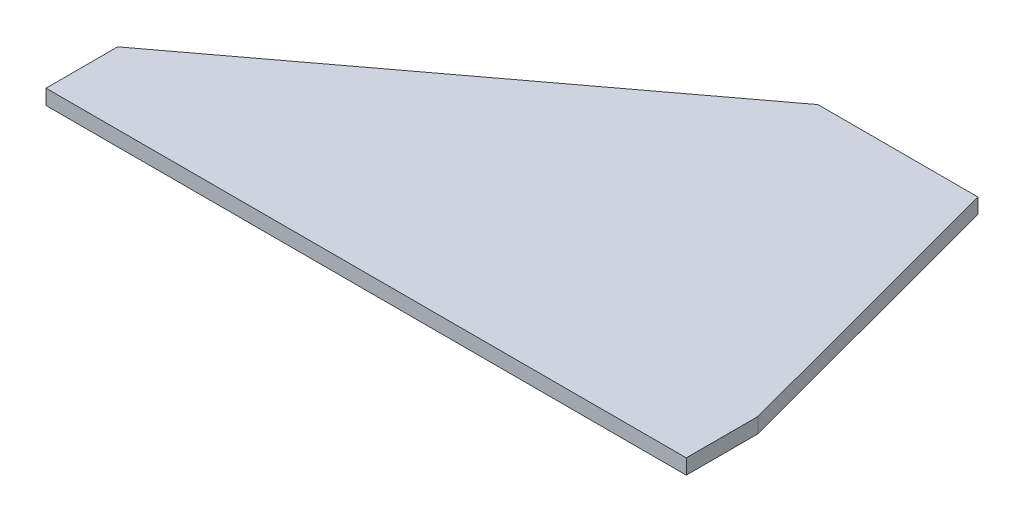
SolidWorks part; units mm, degrees
ref_plane "Front Plane" through (0, 0, 0) normal (0, 0, 1) x (1, 0, 0)
ref_plane "Top Plane" through (0, 0, 0) normal (0, 1, 0) x (1, 0, 0)
ref_plane "Right Plane" through (0, 0, 0) normal (1, 0, 0) x (0, 0, -1)
sketch "Sketch1" plane through (0, 0, 0) normal (0, 1, 0) x (1, 0, 0)
  line L0 (0, 0) -> (0, 22.733)
  line L1 (0, 22.733) -> (127, 117.983)
  line L2 (127, 117.983) -> (177.8, 117.983)
  line L3 (177.8, 117.983) -> (203.2, 22.733)
  line L4 (203.2, 22.733) -> (203.2, 0)
  line L5 (203.2, 0) -> (0, 0)
  line L6 (0, 22.733) -> (0, 117.983) construction
  line L7 (0, 117.983) -> (127, 117.983) construction
  dimension "D1" = 203.2
  dimension "D2" = 22.733
  dimension "D3" = 50.8
  dimension "D4" = 95.25
  dimension "D5" = 127
extrude "Boss-Extrude1" add sketch "Sketch1" along normal blind 2.3813 and the other way blind 2.3813 contours L3 L4 L5 L0 L1 L2
equation "\"Root Chord\"= 8"
equation "\"Tip Chord\"=2"
equation "\"Height\"=3.75"
equation "\"Sweep Length\"=5"
equation "\"Fin Thickness\"= 3 / 16"
equation "\"Bevel Depth\"= 1 / 16"
equation "\"Bevel Width\"= 1 / 4"
equation "\"Tab Height\"=0.895"
equation "\"D2@Sketch1\"=\"Tab Height\""
equation "\"D4@Sketch1\"=\"Height\""
equation "\"D5@Sketch1\"=\"Sweep Length\""
equation "\"D3@Sketch1\"=\"Tip Chord\""
equation "\"D1@Sketch1\"=\"Root Chord\""
equation "\"D1@Boss-Extrude1\"=\"Fin Thickness\"/2"
equation "\"D2@Boss-Extrude1\"=\"Fin Thickness\"/2"
equation "\"D1@Chamfer2\"=\"Bevel Depth\""
equation "\"D3@Chamfer2\"=\"Bevel Width\""
